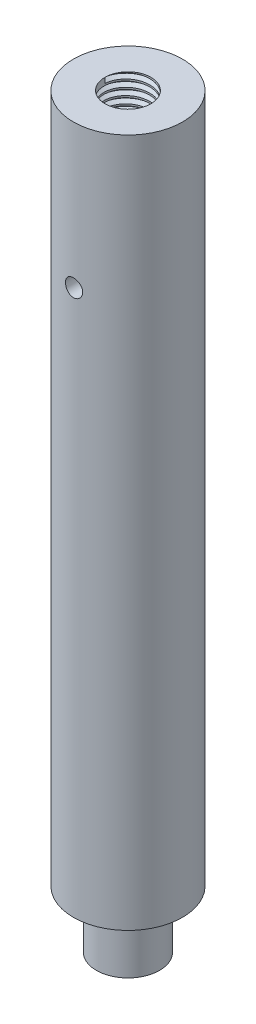
SolidWorks part; units mm, degrees
ref_plane "Alzado" through (0, 0, 0) normal (0, 0, 1) x (1, 0, 0)
ref_plane "Planta" through (0, 0, 0) normal (0, 1, 0) x (1, 0, 0)
ref_plane "Vista lateral" through (0, 0, 0) normal (1, 0, 0) x (0, 0, -1)
sketch "Croquis1" plane through (0, 0, 0) normal (0, 1, 0) x (1, 0, 0)
  circle A0 centre (0, 0) radius 9.5
  dimension "D1" = 19
extrude "Saliente-Extruir1" add sketch "Croquis1" along normal blind 120
sketch "Croquis2" plane through (0, 0, 0) normal (0, 0, 1) x (1, 0, 0)
  line L0 (-9.5, 22) -> (-9.5, 32)
  line L1 (-9.5, 120) -> (-9.5, 0) construction
  line L2 (-9.5, 32) -> (-5.5608, 21.3054)
  line L3 (-5.5608, 21.3054) -> (-9.5, 22)
  line L5 (-9.5, 0) -> (9.5, 0) construction
  dimension "D1" = 4
  dimension "D2" = 10
  dimension "D3" = 100
  dimension "D4" = 22
ref_axis "Eje1" through (0, 120, 0) along (0, -1, 0)
sketch "Croquis3" plane through (0, 0, 0) normal (0, -1, 0) x (1, 0, 0)
  circle A0 centre (0, 0) radius 5.5
  dimension "D1" = 11
extrude "Saliente-Extruir2" add sketch "Croquis3" along normal blind 10
sketch "Croquis4" plane through (0, -10, 0) normal (0, -1, 0) x (1, 0, 0)
  circle A0 centre (0, 0) radius 2.5
  dimension "D1" = 5
extrude "Cortar-Extruir1" cut sketch "Croquis4" against normal blind 110
sketch "Croquis5" plane through (0, 0, 0) normal (0, 0, 1) x (1, 0, 0)
  line L0 (0, 120) -> (0, 0) construction
  line L1 (9.5, 120) -> (-9.5, 120) construction
  circle A0 centre (0, 95) radius 1.5
  dimension "D1" = 3
  dimension "D2" = 25
extrude "Cortar-Extruir2" cut sketch "Croquis5" against normal blind 110 and the other way blind 110
sketch "Croquis6" plane through (0, 120, 0) normal (0, 1, 0) x (1, 0, 0)
  circle A0 centre (0, 0) radius 4
  dimension "D1" = 8
extrude "Cortar-Extruir3" cut sketch "Croquis6" against normal blind 10
thread "Rosca1" pitch 1.25 method cut profile "Perfil de rosca1" start angle 0, offset 0, length 0, pitch 1.25, diameter 8
ref_plane "Plano1" through (-4, 120, 0) normal (0, 0, 1) x (-1, 0, 0)
sketch "Perfil de rosca1" plane through (-4, 120, 0) normal (0, 0, 1) x (-1, 0, 0)
  line L0 (0, 0) -> (0, 1.25) construction
  line L1 (0, 0) -> (0.6766, 0.3906)
  line L2 (0.6766, 0.3906) -> (0.6766, 0.5469)
  line L3 (0.6766, 0.5469) -> (0, 0.9375)
  line L4 (0.6766, 0.4687) -> (0, 0.4687) construction
  line L11 (0, 0) -> (0, 0.9375)
  point P2 (0, 0)
  dimension "Pitch" = 1.25
  dimension "Profile_Angle" = 60
  dimension "Profile_Land" = 0.1562
  dimension "Profile_Height" = 0.6766
